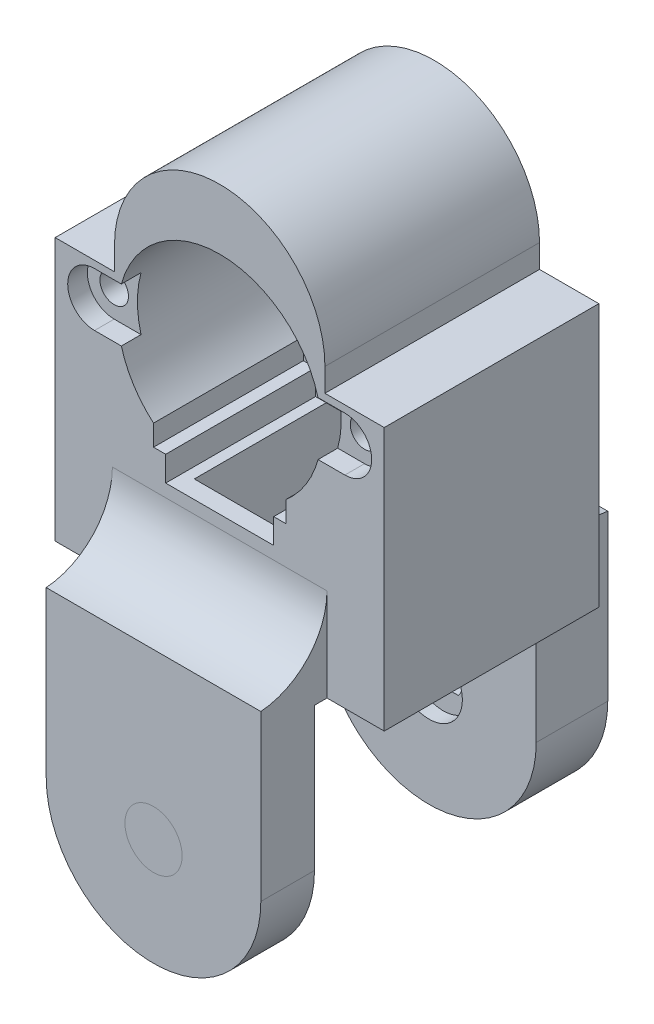
SolidWorks part; units mm, degrees
ref_plane "Front Plane" through (0, 0, 0) normal (0, 0, 1) x (1, 0, 0)
ref_plane "Top Plane" through (0, 0, 0) normal (0, 1, 0) x (1, 0, 0)
ref_plane "Right Plane" through (0, 0, 0) normal (1, 0, 0) x (0, 0, -1)
sketch "Sketch2" plane through (0, 0, 0) normal (0, 0, 1) x (1, 0, 0)
  line L0 (-7.55, 18.2411) -> (-7.55, 14.75)
  line L1 (-7.55, 14.75) -> (7.55, 14.75)
  line L2 (7.55, 14.75) -> (7.55, 18.2411)
  line L3 (7.55, 18.2411) -> (9.25, 18.2411)
  line L4 (9.25, 18.2411) -> (9.25, 21.1603)
  line L5 (-7.55, 18.2411) -> (-9.25, 18.2411)
  line L6 (-9.25, 18.2411) -> (-9.25, 21.1603)
  line L7 (-14.7095, 40) -> (-23, 40)
  line L8 (-23, 40) -> (-23, 0)
  line L10 (14.7095, 40) -> (23, 40)
  line L11 (23, 40) -> (23, 0)
  line L13 (-23, 0) -> (23, 0)
  arc A0 (14.7095, 40) -> (-14.7095, 40) centre (0, 40) ccw
  arc A4 (9.25, 21.1603) -> (-9.25, 21.1603) centre (0, 32) ccw
  point P6 (0, 14.75)
  point P15 (0, 0)
  dimension "D1" = 8.2905
  dimension "D12" = 3.4911
  dimension "D16" = 14.25
  dimension "D17" = 14.7095
  dimension "D2" = 8.2905
  dimension "D3" = 25.25
  dimension "D4" = 40
  dimension "D5" = 0
  dimension "D6" = 0
  dimension "D7" = 46
  dimension "D9" = 2.9191
  dimension "D10" = 1.7
  dimension "D11" = 1.7
  dimension "D13" = 15.1
  dimension "D14" = 2.9191
  dimension "D15" = 3.4911
extrude "Boss-Extrude1" add sketch "Sketch2" along normal blind 20.95
sketch "Sketch3" plane through (0, 0, 0) normal (0, 0, 1) x (1, 0, 0)
  line L7 (-14.7095, 40) -> (-23, 40)
  line L8 (-23, 40) -> (-23, 0)
  line L9 (14.7095, 40) -> (23, 40)
  line L10 (23, 40) -> (23, 0)
  line L11 (-23, 0) -> (23, 0)
  line L12 (23, 40) -> (14.7095, 40) construction
  line L13 (-23, 40) -> (-23, 0) construction
  line L17 (-23, 0) -> (23, 0) construction
  line L19 (23, 0) -> (23, 40) construction
  arc A0 (14.7095, 40) -> (-14.7095, 40) centre (0, 40) ccw
  arc A1 (14.7095, 40) -> (-14.7095, 40) centre (0, 40) ccw construction
  dimension "D1" = 0
extrude "Boss-Extrude2" add sketch "Sketch3" against normal blind 9.05
sketch "Sketch6" plane through (0, 0, 20.95) normal (0, 0, 1) x (1, 0, 0)
  line L0 (-14.7095, 40) -> (-23, 40) construction
  line L1 (-23, 40) -> (-23, 0) construction
  line L2 (23, 40) -> (14.7095, 40) construction
  line L3 (23, 0) -> (23, 40) construction
  circle A0 centre (-17.5, 32) radius 2
  circle A1 centre (17.5, 32) radius 2
  dimension "D1" = 8
  dimension "D2" = 5.5
  dimension "D3" = 4
  dimension "D4" = 8
  dimension "D5" = 5.5
  dimension "D6" = 4
extrude "Cut-Extrude2" cut sketch "Sketch6" against normal blind 10
sketch "Sketch7" plane through (0, 0, 20.95) normal (0, 0, 1) x (1, 0, 0)
  line L0 (-17.5, 32) -> (17.5, 32) construction
  line L3 (-17.5, 35.75) -> (17.5, 35.75)
  line L4 (-17.5, 28.25) -> (17.5, 28.25)
  arc A2 (-17.5, 35.75) -> (-17.5, 28.25) centre (-17.5, 32) ccw
  arc A3 (17.5, 28.25) -> (17.5, 35.75) centre (17.5, 32) ccw
  circle A4 centre (-17.5, 32) radius 2 construction
  circle A5 centre (-17.5, 32) radius 2 construction
  circle A6 centre (17.5, 32) radius 2 construction
  point P2 (0, 32)
  dimension "D2" = 7.5
  dimension "D3" = 1.75
  dimension "D4" = 1.75
  dimension "D1" = 3.75
extrude "Cut-Extrude3" cut sketch "Sketch7" against normal blind 2.75
sketch "Sketch8" plane through (0, 0, 20.95) normal (0, 0, 1) x (1, 0, 0)
  line L0 (-14.7095, 40) -> (-23, 40) construction
  line L1 (-14.7095, 40) -> (-23, 40)
  line L2 (-14.7095, 40) -> (-14.7095, 36.75)
  line L3 (-14.7095, 36.75) -> (-23, 36.75)
  line L4 (-23, 40) -> (-23, 36.75)
  line L5 (14.7095, 40) -> (23, 40)
  line L6 (14.7095, 40) -> (14.7095, 36.75)
  line L7 (14.7095, 36.75) -> (23, 36.75)
  line L8 (23, 40) -> (23, 36.75)
  line L9 (-23, 40) -> (-23, 0) construction
  line L10 (-13.7477, 35.75) -> (-17.5, 35.75) construction
  line L11 (17.5, 35.75) -> (13.7477, 35.75) construction
  line L12 (23, 0) -> (23, 40) construction
  line L13 (23, 40) -> (14.7095, 40) construction
  dimension "D2" = 1
  dimension "D3" = 1
extrude "Cut-Extrude4" cut sketch "Sketch8" along normal through all both and the other way through all
sketch "Sketch11" plane through (0, 0, -9.05) normal (0, 0, -1) x (-1, 0, 0)
  circle A0 centre (0, 40) radius 11.15
  arc A1 (14.7095, 40) -> (-14.7095, 40) centre (0, 40) ccw construction
  dimension "D1" = 22.3
extrude "Bearing Hole" cut sketch "Sketch11" against normal blind 7.3
sketch "Sketch9" plane through (0, 14.75, -19.25) normal (0, 1, 0) x (-1, 0, 0)
  line L0 (7.55, 40.2) -> (-7.55, 40.2) construction
  line L1 (-6.05, 37.7) -> (6.05, 37.7)
  line L2 (-6.05, 37.7) -> (-6.05, 16.2)
  line L3 (-6.05, 16.2) -> (6.05, 16.2)
  line L4 (6.05, 37.7) -> (6.05, 16.2)
  line L8 (-7.55, 40.2) -> (-7.55, 19.25) construction
  line L9 (7.55, 40.2) -> (7.55, 19.25) construction
  line L10 (7.55, 10.2) -> (-7.55, 10.2) construction
  dimension "D1" = 2.5
  dimension "D2" = 1.5
  dimension "D3" = 1.5
  dimension "D4" = 6
extrude "Wire Hole" cut sketch "Sketch9" against normal through all
sketch "Sketch12" plane through (0, 0, 0) normal (0, -1, 0) x (1, 0, 0)
  line L0 (-23, -9.05) -> (23, -9.05) construction
  line L1 (-23, -9.05) -> (23, -9.05)
  line L2 (-23, -9.05) -> (-23, 20.95)
  line L3 (-23, 20.95) -> (23, 20.95)
  line L4 (23, -9.05) -> (23, 20.95)
  line L5 (-23, 20.95) -> (23, 20.95) construction
  line L7 (-23, 20.95) -> (-23, -9.05) construction
  point P4 (0, -9.05)
  dimension "D1" = 0
  dimension "D2" = 0
  dimension "D3" = 0
  dimension "D4" = 0
extrude "Boss-Extrude3" add sketch "Sketch12" along normal blind 0.0001
sketch "Sketch13" plane through (0, 0, 20.95) normal (0, 0, 1) x (1, 0, 0)
  line L0 (-15, -0.0001) -> (15, -0.0001)
  line L1 (23, -0.0001) -> (-23, -0.0001) construction
  line L2 (15, -0.0001) -> (15, -20.0001)
  line L3 (-15, -0.0001) -> (-15, -20.0001)
  line L4 (0, -16.5001) -> (0, 16.5001) construction
  arc A0 (-15, -20.0001) -> (15, -20.0001) centre (0, -20.0001) ccw
  point P7 (0, -0.0001)
  dimension "D1" = 15
  dimension "D2" = 0
  dimension "D3" = 20
extrude "Boss-Extrude4" add sketch "Sketch13" along normal blind 9.25 and the other way blind 39.25
sketch "Sketch14" plane through (-15, 0, 0) normal (-1, 0, 0) x (0, 0, 1)
  line L0 (20.95, -0.0001) -> (30.2, -0.0001) construction
  line L1 (22.7, -35.0001) -> (-8.3, -35.0001)
  line L2 (22.7, -35.0001) -> (22.7, -0.0001)
  line L3 (22.7, -0.0001) -> (-8.3, -0.0001)
  line L4 (-8.3, -35.0001) -> (-8.3, -0.0001)
  line L6 (-18.3, -35.0001) -> (30.2, -35.0001) construction
  line L7 (30.2, -0.0001) -> (30.2, -20.0001) construction
  dimension "D1" = 31
  dimension "D2" = 0
  dimension "D3" = 0
  dimension "D4" = 7.5
extrude "Cut-Extrude5" cut sketch "Sketch14" against normal through all
sketch "Sketch15" plane through (0, 0, 30.2) normal (0, 0, 1) x (1, 0, 0)
  circle A0 centre (0, -20.0001) radius 4
  arc A2 (-15, -20.0001) -> (15, -20.0001) centre (0, -20.0001) ccw construction
  dimension "D1" = 8
extrude "Cut-Extrude6" cut sketch "Sketch15" against normal through all
sketch "Sketch17" plane through (0, 0, -18.3) normal (0, 0, -1) x (-1, 0, 0)
  line L0 (-2.1213, -18.2501) -> (2.1213, -18.2501)
  line L1 (-2.1213, -21.7501) -> (2.1213, -21.7501)
  arc A0 (-2.1213, -18.2501) -> (-2.1213, -21.7501) centre (0, -20.0001) ccw
  arc A1 (2.1213, -18.2501) -> (2.1213, -21.7501) centre (0, -20.0001) cw
  circle A2 centre (0, -20.0001) radius 6.1696
  circle A4 centre (0, -20.0001) radius 4 construction
  point P9 (0, 0)
  dimension "D3" = 2.75
  dimension "D4" = 2.75
  dimension "D1" = 4.2426
  dimension "D2" = 4.2426
extrude "Boss-Extrude5" add sketch "Sketch17" against normal up to surface (10 mm away) up to face at (-4, -20.0001, -8.3)
sketch "Sketch18" plane through (0, 0, 30.2) normal (0, 0, 1) x (1, 0, 0)
  circle A0 centre (0, -20.0001) radius 4
  circle A1 centre (0, -20.0001) radius 4 construction
  dimension "D1" = 8
extrude "Boss-Extrude6" add sketch "Sketch18" against normal offset from surface (14 mm away) 6.5 separate body up to face at (4, -20.0001, 22.7) offset beyond the face yes
sketch "Sketch19" plane through (0, 0, -8.3) normal (0, 0, 1) x (1, 0, 0)
  circle A0 centre (0, -20.0001) radius 4.675
  circle A1 centre (0, -20.0001) radius 4 construction
  point P2 (0, 0)
  dimension "D1" = 9.35
extrude "Cut-Extrude7" cut sketch "Sketch19" against normal blind 2
sketch "Sketch20" plane through (0, 0, 20.95) normal (0, 0, 1) x (1, 0, 0)
  line L1 (-15, -0.0001) -> (15, -0.0001)
  line L2 (-15, -0.0001) -> (-15, 2.9999)
  line L3 (-15, 2.9999) -> (15, 2.9999)
  line L4 (15, -0.0001) -> (15, 2.9999)
  dimension "D1" = 3
extrude "Boss-Extrude7" add sketch "Sketch20" along normal up to surface (9.25 mm away) and the other way up to surface (39.25 mm away) up to face at (4, -20.0001, 30.2) other way up to face at (0, -13.7501, -18.3)
fillet "Fillet1" radius 10 2 edges at (0, 2.9999, 20.95) (0, 2.9999, -9.05)
